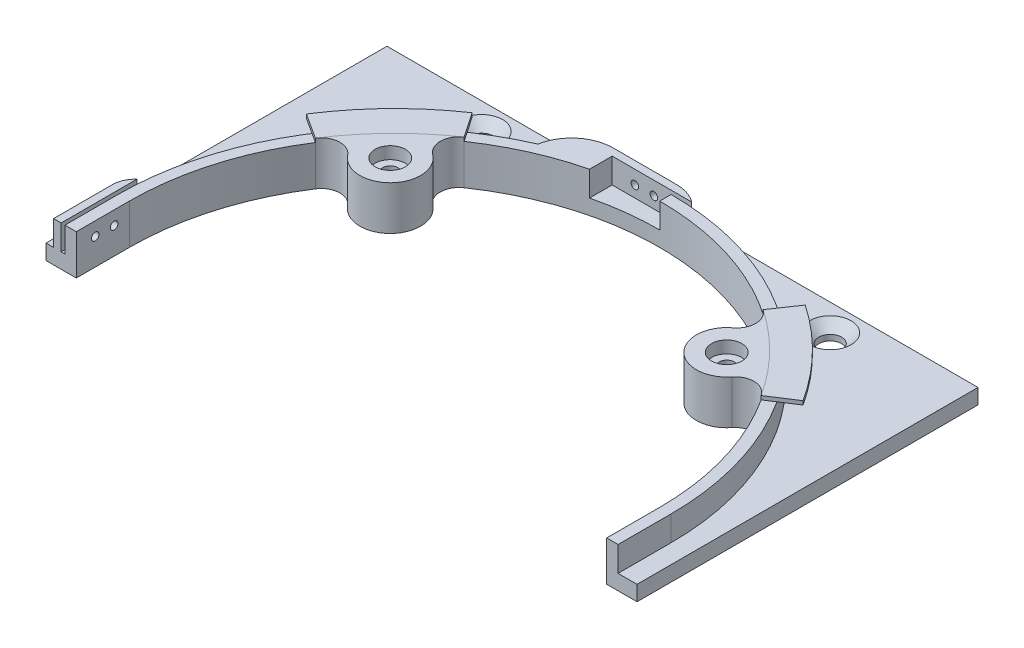
SolidWorks part; units mm, degrees
material "Aluminum"
ref_plane "Front Plane" through (0, 0, 0) normal (0, 0, 1) x (1, 0, 0)
ref_plane "Top Plane" through (0, 0, 0) normal (0, 1, 0) x (1, 0, 0)
ref_plane "Right Plane" through (0, 0, 0) normal (1, 0, 0) x (0, 0, -1)
sketch "Sketch1" plane through (0, 0, 0) normal (0, 1, 0) x (1, 0, 0)
  line L0 (36.5, 0) -> (36.5, -7)
  line L1 (-36.5, 0) -> (-36.5, -7)
  line L2 (-36.5, -7) -> (-35, -7)
  line L3 (35, -7) -> (36.5, -7)
  line L7 (35, 0) -> (35, -7)
  line L8 (-35, 0) -> (-35, -7)
  arc A0 (-35, 0) -> (35, 0) centre (0, 0) cw
  arc A1 (-36.5, 0) -> (36.5, 0) centre (0, 0) cw
  point P0 (0, 0)
  dimension "D2" = 35
  dimension "D1" = 1.5
  dimension "D3" = 7
  dimension "D4" = 7
extrude "Boss-Extrude1" add sketch "Sketch1" along normal blind 3.3
sketch "Sketch2" plane through (0, 0, 0) normal (0, -1, 0) x (1, 0, 0)
  line L0 (-35, 7) -> (-39, 7)
  line L1 (-35, 7) -> (-35, 0) construction
  line L2 (35, 0) -> (35, 7) construction
  line L3 (35, 7) -> (39, 7)
  line L4 (39, 7) -> (39, -38)
  line L5 (39, -38) -> (-39, -38)
  line L6 (-39, -38) -> (-39, 7)
  line L8 (-36.5, 7) -> (-35, 7) construction
  line L9 (35, 7) -> (36.5, 7) construction
  line L10 (-35, 7) -> (-35, 0)
  line L11 (35, 7) -> (35, 0)
  arc A0 (-35, 0) -> (35, 0) centre (0, 0) ccw
  dimension "D1" = 4
  dimension "D2" = 4
  dimension "D3" = 45
extrude "Boss-Extrude2" add sketch "Sketch2" along normal blind 2 separate body
sketch "Sketch3" plane through (0, 3.3, 0) normal (0, 1, 0) x (1, 0, 0)
  line L0 (0, 0) -> (0, 40.1247) construction
  line L1 (0, 0) -> (-39, 38) construction
  arc A0 (-25.3471, 19.1609) -> (-19.8127, 24.841) centre (-22.2031, 21.6338) ccw
  arc A1 (35, 0) -> (-35, 0) centre (0, 0) ccw construction
  arc A2 (-29.413, 18.9703) -> (-19.7278, 28.9105) centre (0, 0) cw
  arc A3 (-25.3471, 19.1609) -> (-29.413, 18.9703) centre (-27.3121, 17.6153) ccw
  arc A4 (-19.8127, 24.841) -> (-19.7278, 28.9105) centre (-18.3187, 26.8454) cw
  arc A5 (-25.3471, 19.1609) -> (-29.413, 18.9703) centre (-27.3121, 17.6153) ccw
  arc A6 (-19.8127, 24.841) -> (-19.7278, 28.9105) centre (-18.3187, 26.8454) cw
  arc A7 (19.8127, 24.841) -> (19.7278, 28.9105) centre (18.3187, 26.8454) ccw
  arc A8 (25.3471, 19.1609) -> (29.413, 18.9703) centre (27.3121, 17.6153) cw
  arc A9 (19.8127, 24.841) -> (19.7278, 28.9105) centre (18.3187, 26.8454) ccw
  arc A10 (25.3471, 19.1609) -> (29.413, 18.9703) centre (27.3121, 17.6153) cw
  arc A11 (29.413, 18.9703) -> (19.7278, 28.9105) centre (0, 0) ccw
  arc A12 (25.3471, 19.1609) -> (19.8127, 24.841) centre (22.2031, 21.6338) cw
  arc M5 (-35, 0) -> (35, 0) centre (0, 0) cw
  dimension "D1" = 8
  dimension "D2" = 2.5
extrude "Boss-Extrude3" add sketch "Sketch3" against normal blind 5.3 and the other way blind 0.5 contours A0 A4 A3 M5 | A12 A8 A7 M5 region at (-22.5616, 3.3, -21.9831) region at (22.5616, 3.3, -21.9831)
sketch "Sketch9" plane through (0, 3.3, 0) normal (0, 1, 0) x (1, 0, 0)
  line L0 (0, 0) -> (0, 35) construction
  line L1 (0, 0) -> (-25.8094, 25.8094) construction
  line L2 (-29.413, 18.9703) -> (-32.7745, 21.1384)
  line L3 (-19.7278, 28.9105) -> (-21.9824, 32.2145)
  line L4 (29.413, 18.9703) -> (32.7745, 21.1384)
  line L5 (19.7278, 28.9105) -> (21.9824, 32.2145)
  arc A0 (19.7278, 28.9105) -> (-19.7278, 28.9105) centre (0, 0) ccw construction
  arc A1 (36.5, 0) -> (-36.5, 0) centre (0, 0) ccw construction
  arc A2 (-29.413, 18.9703) -> (-19.7278, 28.9105) centre (0, 0) cw
  arc A3 (-32.7745, 21.1384) -> (-21.9824, 32.2145) centre (0, 0) cw
  arc A4 (21.9824, 32.2145) -> (32.7745, 21.1384) centre (0, 0) cw
  arc A5 (-35, 0) -> (35, 0) centre (0, 0) cw construction
  arc A6 (-39, 0) -> (39, 0) centre (0, 0) cw construction
  arc A7 (0, 35) -> (29.413, 18.9703) centre (0, 0) cw
  arc A8 (-29.413, 18.9703) -> (-19.7278, 28.9105) centre (0, 0) cw
  arc M3 (36.5, 0) -> (-36.5, 0) centre (0, 0) ccw
  dimension "D1" = 4
extrude "Boss-Extrude4" add sketch "Sketch9" along normal blind 0.5 separate body contours A3 L2 L3 M3 | L2 A2 L3 M3 | L5 A7 L4 M3 | A4 L5 L4 M3 | L5 A4 L4 A7 region at (26.8683, 3.3, -26.1794) region at (25.4393, 3.3, -24.787) region at (-25.4393, 3.3, -24.787) region at (-26.8683, 3.3, -26.1794)
hole_wizard "CBORE for M2 Pan Head Screw2" positions "Sketch12" profile "Sketch11" counterbore size "M2" standard "ISO"
sketch "Sketch12" plane through (0, 3.8, 0) normal (0, 1, 0) x (1, 0, 0)
  point P0 (-22.2031, 21.6338)
  point P3 (22.2031, 21.6338)
sketch "Sketch11" plane through (-22.2031, 3.8, -21.6338) normal (1, 0, 0) x (0, 0, 1)
  line L0 (0, 0) -> (0, 30.6009)
  line L1 (0, 30.6009) -> (1, 30)
  line L2 (1, 30) -> (1, 1.6)
  line L3 (1, 1.6) -> (2, 1.6)
  line L4 (2, 1.6) -> (2, 0)
  line L5 (2, 0) -> (0, 0)
  line L10 (0, 30.6009) -> (-1, 30) construction
  line L11 (0, -6.35) -> (0, 107.95) construction
  dimension "Hole Dia." = 2
  dimension "Hole Depth" = 30
  dimension "C'Bore Dia." = 4
  dimension "C'Bore Depth" = 1.6
  dimension "Drill Angle" = 118
sketch "Sketch13" plane through (0, 0, 7) normal (0, 0, 1) x (1, 0, 0)
  line L0 (-36.5, 3.3) -> (-35, 3.3) construction
  line L1 (-37, -0.1947) -> (-38, -0.1947)
  line L2 (-37, -0.1947) -> (-37, 3.3)
  line L3 (-37, 3.3) -> (-38, 3.3)
  line L4 (-38, -0.1947) -> (-38, 3.3)
  line L5 (-36.5, 3.3) -> (-36.5, 0) construction
  dimension "D1" = 0.5
  dimension "D2" = 1
extrude "Boss-Extrude5" add sketch "Sketch13" against normal blind 10
fillet "Fillet1" radius 3 1 edges at (-38, 1.65, -3)
sketch "Sketch15" plane through (0, 3.3, 0) normal (0, 1, 0) x (1, 0, 0)
  line L0 (0, 36.5) -> (0, 14.064) construction
  line L3 (0, 36.5) -> (-8.2799, 36.5)
  line L4 (0, 36.5) -> (0, 27.5592)
  line L5 (0, 27.5592) -> (-8.2799, 27.5592)
  line L6 (-8.2799, 36.5) -> (-8.2799, 27.5592)
  arc A0 (36.5, 0) -> (-36.5, 0) centre (0, 0) ccw construction
extrude "Cut-Extrude2" cut sketch "Sketch15" against normal blind 3.3
hole_wizard "Ø1.0 (1) Diameter Hole2" positions "Sketch20" profile "Sketch19" hole size "Ø1.0" standard "ANSI Metric"
sketch "Sketch20" plane through (-35, 0, 0) normal (1, 0, 0) x (0, 0, -1)
  line L0 (-7, 3.3) -> (-7, -2) construction
  line L1 (-7, 3.3) -> (0, 3.3) construction
  line L2 (0.7639, 3.3) -> (-7, 3.3) construction
  point P0 (-4.5, 1.5)
  point P2 (-2, 1.5)
  dimension "D1" = 2.5
  dimension "D2" = 2.5
  dimension "D3" = 1.8
  dimension "D4" = 1.8
sketch "Sketch19" plane through (-35, 1.5, 4.5) normal (0, 1, 0) x (0, 0, -1)
  line L0 (0, 0) -> (0, 5)
  line L1 (0, 5) -> (0.5, 5)
  line L2 (0.5, 5) -> (0.5, 0)
  line L5 (0.5, 0) -> (0, 0)
  line L10 (0, 5) -> (-0.5, 5) construction
  line L11 (0, -6.35) -> (0, 107.95) construction
  dimension "Hole Dia." = 1
  dimension "Hole Depth" = 5
  dimension "Drill Angle" = 180
sketch "Sketch21" plane through (0, 0, 0) normal (0, 1, 0) x (1, 0, 0)
  line L0 (0, 36.5) -> (7.1075, 36.5) construction
  line L1 (-0.2799, 37) -> (2.2201, 37)
  line L2 (2.2201, 38) -> (2.2201, 37)
  line L3 (-14.5537, 38) -> (2.2201, 38)
  line L4 (-8.2799, 34.0065) -> (-8.2799, 37)
  line L5 (-8.2799, 37) -> (-0.2799, 37)
  line L6 (-8.2799, 30.5823) -> (-8.2799, 35.8175) construction
  line L7 (-39, 38) -> (39, 38) construction
  line L8 (-8.2799, 34.0065) -> (-14.5537, 32.511)
  line L12 (-14.5537, 38) -> (-14.5537, 32.511)
  dimension "D4" = 8
  dimension "D1" = 2.5
  dimension "D2" = 1
extrude "Boss-Extrude6" add sketch "Sketch21" along normal blind 3.3 contours L3 L2 L1 L5 L4 L8 L12
fillet "Fillet2" radius 5.5 1 edges at (-14.5537, 1.65, -38)
hole_wizard "CSK for M3 Countersunk Flat Head Screw1" positions "Sketch23" profile "Sketch22" countersink size "M3" standard "ISO" end condition up to next
sketch "Sketch23" plane through (0, 0, 0) normal (0, 1, 0) x (1, 0, 0)
  point P0 (-23, 34.5)
  point P3 (23, 34.5)
sketch "Sketch22" plane through (-23, 0, -34.5) normal (1, 0, 0) x (0, 0, 1)
  line L0 (0, 0) -> (0, 2.001)
  line L1 (0, 2.001) -> (1.5, 2.001)
  line L2 (1.5, 2.001) -> (1.5, 1.25)
  line L3 (1.5, 1.25) -> (2.75, 0)
  line L5 (2.75, 0) -> (0, 0)
  line L6 (-1.5, 1.25) -> (-2.75, 0) construction
  line L11 (0, -6.35) -> (0, 107.95) construction
  dimension "Thru Hole Dia." = 3
  dimension "Thru Hole Depth" = 2.001
  dimension "Near C'Sink Dia." = 5.5
  dimension "Near C'Sink Angle" = 90
fillet "Fillet3" radius 5 1 edges at (2.2201, 1.65, -38)
hole_wizard "Ø1.0 (1) Diameter Hole3" positions "Sketch25" profile "Sketch24" hole size "Ø1.0" standard "ANSI Metric" end condition through all
sketch "Sketch25" plane through (0, 0, -37) normal (0, 0, 1) x (1, 0, 0)
  point P0 (-5.2799, 1.5)
  point P3 (-2.7799, 1.5)
sketch "Sketch24" plane through (-5.2799, 1.5, -37) normal (1, 0, 0) x (0, -1, 0)
  line L0 (0, 0) -> (0, 1)
  line L1 (0, 1) -> (0.5, 1)
  line L2 (0.5, 1) -> (0.5, 0)
  line L5 (0.5, 0) -> (0, 0)
  line L11 (0, -6.35) -> (0, 107.95) construction
  dimension "Thru Hole Dia." = 1
  dimension "Thru Hole Depth" = 1
